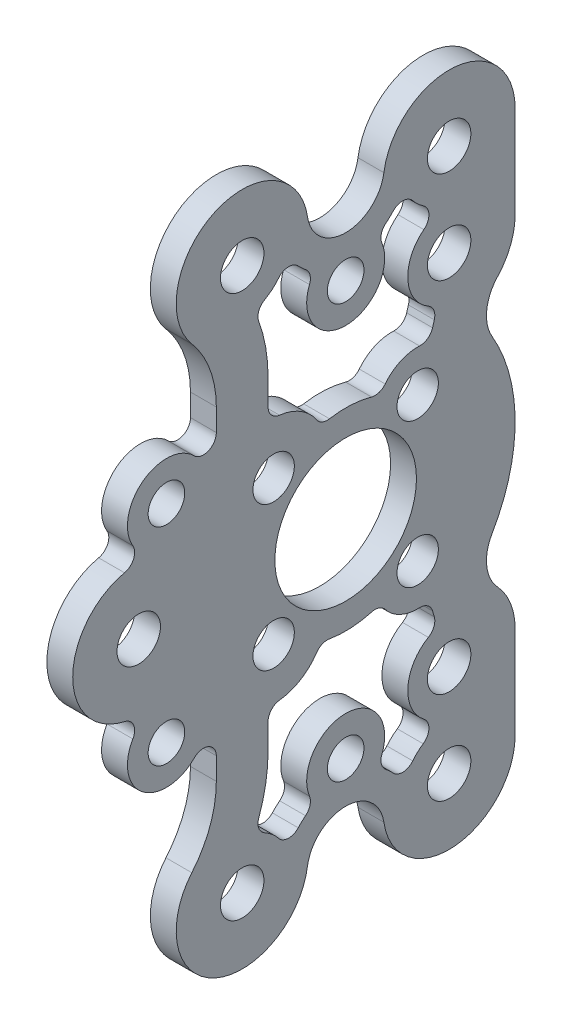
SolidWorks part; units mm, degrees
material "AR500"
ref_plane "Front Plane" through (0, 0, 0) normal (0, 0, 1) x (1, 0, 0)
ref_plane "Top Plane" through (0, 0, 0) normal (0, 1, 0) x (1, 0, 0)
ref_plane "Right Plane" through (0, 0, 0) normal (1, 0, 0) x (0, 0, -1)
ref_plane "Motor Front Plane" through (39.075, 0, 0) normal (1, 0, 0) x (0, 0, -1)
sketch "Sketch1" plane through (39.075, 0, 0) normal (1, 0, 0) x (0, 0, -1)
  line L1 (12.7, 21.997) -> (-25.4, 0) construction
  line L3 (12.7, 21.997) -> (12.7, -21.997) construction
  line L4 (-25.4, 0) -> (12.7, -21.997) construction
  line L5 (20.8, 21.997) -> (20.8, 32.6221) construction
  circle A0 centre (8.8388, -8.8388) radius 1.65 construction
  circle A1 centre (8.8388, 8.8388) radius 1.65 construction
  circle A2 centre (-8.8388, -8.8388) radius 1.65 construction
  circle A3 centre (-8.8388, 8.8388) radius 1.65 construction
  circle A4 centre (8.8388, -8.8388) radius 1.65 construction
  circle A5 centre (8.8388, 8.8388) radius 1.65 construction
  circle A6 centre (-8.8388, -8.8388) radius 1.65 construction
  circle A7 centre (-8.8388, 8.8388) radius 1.65 construction
  circle A8 centre (0, 0) radius 20.8 construction
  circle A9 centre (0, 0) radius 8.69
  circle A10 centre (-8.8388, 8.8388) radius 2.54
  circle A11 centre (8.8388, 8.8388) radius 2.54
  circle A12 centre (8.8388, -8.8388) radius 2.54
  circle A13 centre (-8.8388, -8.8388) radius 2.54
  circle A14 centre (-8.8388, 8.8388) radius 3.81 construction
  circle A16 centre (12.7, 21.997) radius 2.667
  circle A18 centre (12.7, -21.997) radius 2.667
  circle A19 centre (-25.4, 0) radius 2.667
  arc A20 (-19.925, -5.9695) -> (4.7928, -20.2403) centre (0, 0) ccw
  arc A21 (-19.925, 5.9695) -> (4.7928, 20.2403) centre (0, 0) cw
  arc A23 (15.1322, 14.2708) -> (15.1322, -14.2708) centre (0, 0) cw
  arc A24 (-19.925, -5.9695) -> (-19.925, 5.9695) centre (-25.4, 0) cw
  arc A25 (4.7928, 20.2403) -> (15.1322, 14.2708) centre (12.7, 21.997) cw
  arc A27 (4.7928, -20.2403) -> (15.1322, -14.2708) centre (12.7, -21.997) ccw
  circle A28 centre (0, 0) radius 25.4 construction
  dimension "D1" = 41.6
  dimension "D2" = 5.08
  dimension "D3" = 7.62
  dimension "D4" = 5.334
  dimension "D5" = 50.8
extrude "Boss-Extrude1" add sketch "Sketch1" along normal blind 3.175
fillet "Fillet1" radius 5.08 6 edges at (40.6625, 5.9695, 19.925) (40.6625, -14.2708, -15.1322) (40.6625, -20.2403, -4.7928) (40.6625, -5.9695, 19.925) (40.6625, 20.2403, -4.7928) (40.6625, 14.2708, -15.1322)
sketch "Sketch2" plane through (42.25, 0, 0) normal (1, 0, 0) x (0, 0, -1)
  line L0 (-12.7, -33.3375) -> (-12.7, 33.3375) construction
  line L5 (0, 0) -> (-12.7, 0) construction
  line L6 (0, 0) -> (0, 30.48) construction
  line L11 (12.7, 33.3375) -> (12.7, 21.997) construction
  line L13 (20.8, 33.3375) -> (20.8, 21.997)
  line L14 (-15.875, 19.8978) -> (-15.875, 13.4397)
  line L15 (11.7095, 24.4733) -> (-15.875, 13.4397)
  arc A24 (-4.6874, 34.5243) -> (-18.8821, 28.1038) centre (-12.7, 33.3375) ccw
  circle A27 centre (-12.7, 33.3375) radius 2.667
  circle A32 centre (12.7, 33.3375) radius 2.667
  arc A33 (4.6874, 34.5243) -> (20.8, 33.3375) centre (12.7, 33.3375) cw
  circle A34 centre (-25.4, 0) radius 2.667 construction
  arc A35 (-4.6874, 34.5243) -> (4.6874, 34.5243) centre (0, 35.2185) ccw
  arc A39 (18.6368, 16.4866) -> (4.9595, 24.3833) centre (12.7, 21.997) ccw construction
  arc A40 (-18.8821, 28.1038) -> (-15.875, 19.8978) centre (-28.575, 19.8978) cw
  arc A41 (0.0843, 20.7998) -> (-18.0553, 10.3269) centre (0, 0) ccw construction
  arc A42 (20.8, 21.997) -> (11.7095, 24.4733) centre (14.614, 17.2119) ccw
  circle A43 centre (12.7, 21.997) radius 2.667 construction
  dimension "D3" = 30.48
  dimension "D1" = 6.35
  dimension "D4" = 12.7
  dimension "D2" = 66.675
extrude "Boss-Extrude2" add sketch "Sketch2" against normal up to surface (3.175 mm away) up to face at (39.075, -21.997, -15.367)
sketch "Sketch3" plane through (39.075, 0, 0) normal (-1, 0, 0) x (0, 0, 1)
  line L0 (-11.2696, 17.1226) -> (-10.2692, 13.7133)
  line L1 (-12.7, 33.3375) -> (-12.7, 21.997)
  line L2 (9.525, 15.1517) -> (9.525, 19.8978)
  line L3 (15.875, 19.8978) -> (15.875, 13.4397) construction
  circle A0 centre (-12.7, 21.997) radius 5.08
  circle A1 centre (-8.8388, 8.8388) radius 5.08
  circle A2 centre (8.8388, 8.8388) radius 6.35
  circle A3 centre (12.7, 33.3375) radius 5.715
  circle A4 centre (-12.7, 33.3375) radius 5.715
  arc A5 (-7.1743, 31.8788) -> (7.1743, 31.8788) centre (0, 35.2185) ccw
  arc A6 (-4.6874, 34.5243) -> (4.6874, 34.5243) centre (0, 35.2185) ccw construction
  arc A7 (-9.5127, 28.5938) -> (-9.597, 26.0192) centre (-8.6273, 27.2762) ccw
  circle A8 centre (0, 0) radius 11.865
  circle A9 centre (0, 0) radius 8.69 construction
  arc A10 (9.525, 19.8978) -> (11.2461, 27.8105) centre (28.575, 19.8978) cw
  arc A11 (18.8821, 28.1038) -> (15.875, 19.8978) centre (28.575, 19.8978) ccw construction
  dimension "D1" = 11.43
  dimension "D2" = 10.16
  dimension "D3" = 3.175
  dimension "D4" = 1.5875
  dimension "D5" = 3.175
  dimension "D7" = 12.7
  dimension "D6" = 6.35
extrude "Cut-Extrude1" cut sketch "Sketch3" against normal through all contours L2 A10 A3 A5 A4 A7 A0 L0 A1 A8 A2 region at (39.075, 20.9217, 0.0796)
sketch "Sketch4" plane through (39.075, 0, 0) normal (-1, 0, 0) x (0, 0, 1)
  line L0 (0, 0) -> (0, 25.4) construction
  line L1 (0, 0) -> (21.997, 12.7) construction
  line L2 (15.875, 19.8978) -> (15.875, 13.4397) construction
  circle A0 centre (0, 25.4) radius 2.2479 construction
  circle A1 centre (0, 25.4) radius 4.7879
  circle A2 centre (0, 25.4) radius 3.9624 construction
  arc A4 (26.1205, 10.2667) -> (18.5916, 16.0656) centre (21.997, 12.7) ccw
  arc A5 (15.875, 17.1815) -> (18.5916, 16.0656) centre (17.4625, 17.1815) ccw
  arc A6 (26.1205, 10.2667) -> (27.1456, 7.9097) centre (27.4877, 9.4599) ccw
  arc A7 (23.5962, -7.8966) -> (23.5962, 7.8966) centre (25.4, 0) ccw construction
  arc A8 (15.875, 17.1815) -> (27.1456, 7.9097) centre (21.3119, 12.3044) ccw
  point P16 (0, 0)
  dimension "D1" = 4.4958
  dimension "D2" = 2.54
  dimension "D3" = 7.9248
  dimension "D6" = 1.5875
  dimension "D4" = 25.4
  dimension "D5" = 60
extrude "Boss-Extrude3" add sketch "Sketch4" against normal up to surface (3.175 mm away) up to face at (42.25, 21.997, -15.367)
sketch "Sketch7" plane through (39.075, 0, 0) normal (-1, 0, 0) x (0, 0, 1)
  point P0 (0, 25.4)
  point P4 (21.997, 12.7)
hole_wizard "#8 Clearance Hole1" positions "Sketch7" profile "Sketch6" hole size "#8" standard "ANSI Inch" end condition up to next
sketch "Sketch6" plane through (39.075, 25.4, 0) normal (0, 1, 0) x (0, 0, 1)
  line L0 (0, 0) -> (0, 3.175)
  line L1 (0, 3.175) -> (2.2479, 3.175)
  line L2 (2.2479, 3.175) -> (2.2479, 0)
  line L5 (2.2479, 0) -> (0, 0)
  line L11 (0, -6.35) -> (0, 107.95) construction
  dimension "Thru Hole Dia." = 4.4958
  dimension "Thru Hole Depth" = 3.175
fillet "Fillet3" radius 1.5875 10 edges at (40.6625, 11.4644, 3.0571) (40.6625, 11.0684, -4.2742) (40.6625, 13.7133, -10.2692) (40.6625, 17.1226, -11.2696) (40.6625, 31.8788, 7.1743) (40.6625, 27.8105, 11.2461) (40.6625, 15.1517, 9.525) (40.6625, 31.8788, -7.1743) (40.6625, 28.2876, -3.8191) (40.6625, 28.2876, 3.8191)
mirror "Mirror1" about plane through (0, 0, 0) normal (0, 1, 0) of "#8 Clearance Hole1", "Cut-Extrude1", "Fillet3", "Boss-Extrude2", "Boss-Extrude3"
equation "\"D1@Sketch1\"=41.6mm"
